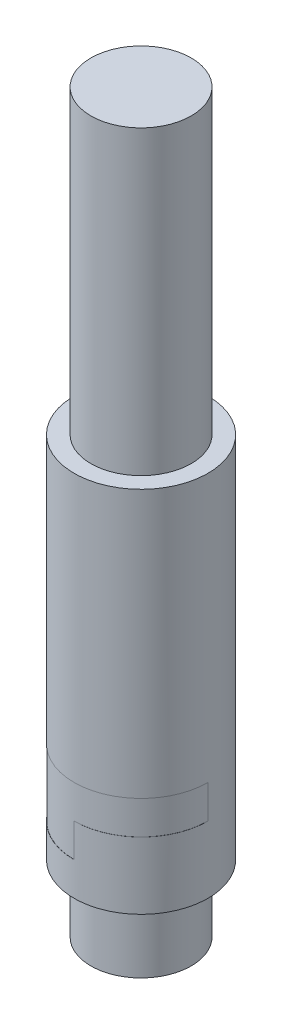
SolidWorks part; units mm, degrees
ref_plane "Front Plane" through (0, 0, 0) normal (0, 0, 1) x (1, 0, 0)
ref_plane "Top Plane" through (0, 0, 0) normal (0, 1, 0) x (1, 0, 0)
ref_plane "Right Plane" through (0, 0, 0) normal (1, 0, 0) x (0, 0, -1)
sketch "Sketch1" plane through (0, 0, 0) normal (0, 1, 0) x (1, 0, 0)
  circle A0 centre (0, 0) radius 9.525
  dimension "D1" = 19.05
extrude "Boss-Extrude1" add sketch "Sketch1" along normal blind 57.15
sketch "Sketch2" plane through (0, 0, 0) normal (0, -1, 0) x (1, 0, 0)
  circle A0 centre (0, 0) radius 12.7
  dimension "D1" = 25.4
extrude "Boss-Extrude2" add sketch "Sketch2" along normal blind 69.85
sketch "Sketch3" plane through (0, -69.85, 0) normal (0, -1, 0) x (1, 0, 0)
  circle A0 centre (0, 0) radius 9.525
  dimension "D1" = 19.05
extrude "Boss-Extrude3" add sketch "Sketch3" along normal blind 12.7
ref_plane "Plane1" through (0, -63.5, 0) normal (0, -1, 0) x (-1, 0, 0)
sketch "Sketch4" plane through (0, -63.5, 0) normal (0, -1, 0) x (-1, 0, 0)
  line L0 (0, 12.7) -> (0, 12.6746)
  line L1 (0, -12.6746) -> (0, -12.7)
  arc A0 (0, -12.7) -> (0, 12.7) centre (0, 0) ccw
  arc A1 (0, -12.6746) -> (0, 12.6746) centre (0, 0) ccw
  circle A2 centre (0, 0) radius 12.7 construction
  dimension "D1" = 0.0254
extrude "Cut-Extrude1" cut sketch "Sketch4" against normal blind 6.35
sketch "Sketch5" plane through (0, -57.15, 0) normal (0, -1, 0) x (1, 0, 0)
  line L0 (-12.7, 0) -> (-12.6746, 0)
  line L1 (12.6746, 0) -> (12.7, 0)
  arc A0 (12.7, 0) -> (-12.7, 0) centre (0, 0) ccw
  circle A1 centre (0, 0) radius 12.7 construction
  arc A2 (12.6746, 0) -> (-12.6746, 0) centre (0, 0) ccw
  dimension "D1" = 0.0254
extrude "Cut-Extrude2" cut sketch "Sketch5" against normal blind 6.35
